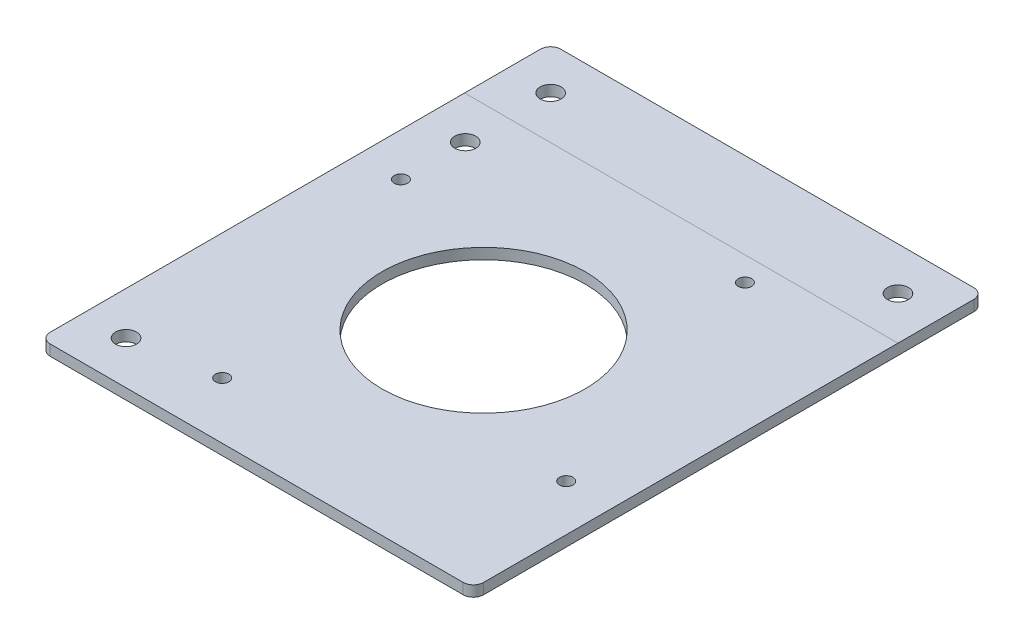
SolidWorks part; units mm, degrees
material "6061-T6 (SS)"
ref_plane "Front Plane" through (0, 0, 0) normal (0, 0, 1) x (1, 0, 0)
ref_plane "Top Plane" through (0, 0, 0) normal (0, 1, 0) x (1, 0, 0)
ref_plane "Right Plane" through (0, 0, 0) normal (1, 0, 0) x (0, 0, -1)
sketch "Sketch1" plane through (0, 0, 0) normal (0, 1, 0) x (1, 0, 0)
  line L0 (1.6095, -585.7621) -> (101.1273, -585.7621) construction
  line L1 (13.1273, -469.9621) -> (141.1273, -469.9621)
  line L3 (13.1273, -620.7621) -> (141.1273, -620.7621)
  line L4 (141.1273, -469.9621) -> (141.1273, -620.7621)
  line L5 (-14.8727, -585.7621) -> (101.1273, -585.7621) construction
  line L6 (101.1273, -585.7621) -> (109.1273, -577.7621) construction
  line L7 (109.1273, -577.7621) -> (109.1273, -528.7621) construction
  line L12 (109.1273, -528.7621) -> (101.1273, -520.7621) construction
  line L13 (101.1273, -520.7621) -> (-3.8527, -520.7621) construction
  line L14 (101.1273, -520.7621) -> (-14.8727, -520.7621) construction
  line L16 (25.8273, -482.6621) -> (13.1273, -482.6621) construction
  line L17 (25.8273, -482.6621) -> (25.8273, -469.9621) construction
  line L18 (128.4273, -482.6621) -> (128.4273, -469.9621) construction
  line L19 (128.4273, -482.6621) -> (141.1273, -482.6621) construction
  line L20 (25.8273, -608.0621) -> (13.1273, -608.0621) construction
  line L21 (25.8273, -608.0621) -> (25.8273, -604.9621) construction
  line L22 (25.8273, -608.0621) -> (25.8273, -620.7621) construction
  line L23 (25.8273, -482.6621) -> (28.9273, -482.6621) construction
  line L24 (13.1273, -531.2621) -> (29.3273, -531.2621) construction
  line L25 (128.4273, -482.6621) -> (128.4273, -485.7621) construction
  line L30 (13.1273, -469.9621) -> (13.1273, -620.7621)
  line L31 (29.3273, -531.2621) -> (-12.8727, -531.2621) construction
  line L32 (25.8273, -482.6621) -> (25.8273, -507.8621) construction
  line L35 (-12.8727, -535.2621) -> (29.3273, -535.2621) construction
  line L36 (13.1273, -535.2621) -> (29.3273, -535.2621) construction
  line L37 (25.8273, -507.8621) -> (28.9273, -507.8621) construction
  circle A0 centre (76.6273, -553.2621) radius 30
  circle A1 centre (25.8273, -482.6621) radius 3.1
  circle A2 centre (128.4273, -482.6621) radius 3.1
  circle A4 centre (25.8273, -608.0621) radius 3.1
  arc A5 (29.3273, -535.2621) -> (29.3273, -531.2621) centre (29.3273, -533.2621) ccw construction
  circle A6 centre (25.8273, -507.8621) radius 3.1
  dimension "D4" = 60
  dimension "D5" = 88
  dimension "D6" = 6.2
  dimension "D1" = 50.8
  dimension "D2" = 35
  dimension "D3" = 32
  dimension "D7" = 12.7
  dimension "D8" = 25.2
extrude "Boss-Extrude1" add sketch "Sketch1" along normal blind 3.175
fillet "Fillet1" radius 3 4 edges at (141.1273, 1.5875, 469.9621) (141.1273, 1.5875, 620.7621) (13.1273, 1.5875, 620.7621) (13.1273, 1.5875, 469.9621)
sketch "Sketch3" plane through (0, 3.175, 0) normal (0, 1, 0) x (1, 0, 0)
  line L0 (25.8273, -482.6621) -> (25.8273, -608.0621) construction
  line L1 (25.8273, -526.8685) -> (103.0209, -502.4621) construction
  line L2 (25.8273, -526.8685) -> (50.2338, -604.0621) construction
  line L3 (50.2338, -604.0621) -> (127.4273, -579.6556) construction
  line L4 (103.0209, -502.4621) -> (127.4273, -579.6556) construction
  line L5 (25.8273, -526.8685) -> (127.4273, -579.6556) construction
  line L6 (50.2338, -604.0621) -> (103.0209, -502.4621) construction
  line L7 (12.8763, -520.1397) -> (109.7497, -489.5111) construction
  line L8 (12.8763, -520.1397) -> (43.505, -617.013) construction
  line L9 (43.505, -617.013) -> (140.3783, -586.3844) construction
  line L10 (109.7497, -489.5111) -> (140.3783, -586.3844) construction
  circle A0 centre (25.8273, -526.8685) radius 1.985
  circle A1 centre (76.6273, -553.2621) radius 30 construction
  circle A2 centre (103.0209, -502.4621) radius 1.985
  circle A3 centre (127.4273, -579.6556) radius 1.985
  circle A4 centre (50.2338, -604.0621) radius 1.985
  point P4 (76.6273, -553.2621)
  point P23 (76.6273, -553.2621)
  dimension "D5" = 3.97
  dimension "D1" = 80.96
  dimension "D2" = 101.6
  dimension "D3" = 90
  dimension "D4" = 90
  dimension "D6" = 4
extrude "Cut-Extrude1" cut sketch "Sketch3" against normal through all
sketch "Sketch4" plane through (0, 3.175, 0) normal (0, 1, 0) x (1, 0, 0)
  line L0 (138.1273, -469.9621) -> (16.1273, -469.9621) construction
  line L4 (13.1273, -495.3621) -> (141.1273, -495.3621)
  line L9 (13.1273, -495.3621) -> (13.1273, -469.9621)
  line L10 (13.1273, -469.9621) -> (141.1273, -469.9621)
  line L11 (141.1273, -495.3621) -> (141.1273, -469.9621)
  line L12 (13.1273, -495.3621) -> (141.1273, -469.9621) construction
  line L13 (13.1273, -469.9621) -> (141.1273, -495.3621) construction
  line L14 (13.1273, -472.9621) -> (13.1273, -617.7621) construction
  point P4 (77.1273, -482.6621)
  dimension "D1" = 25.4
  dimension "D2" = 128
split line "Split Line2"
